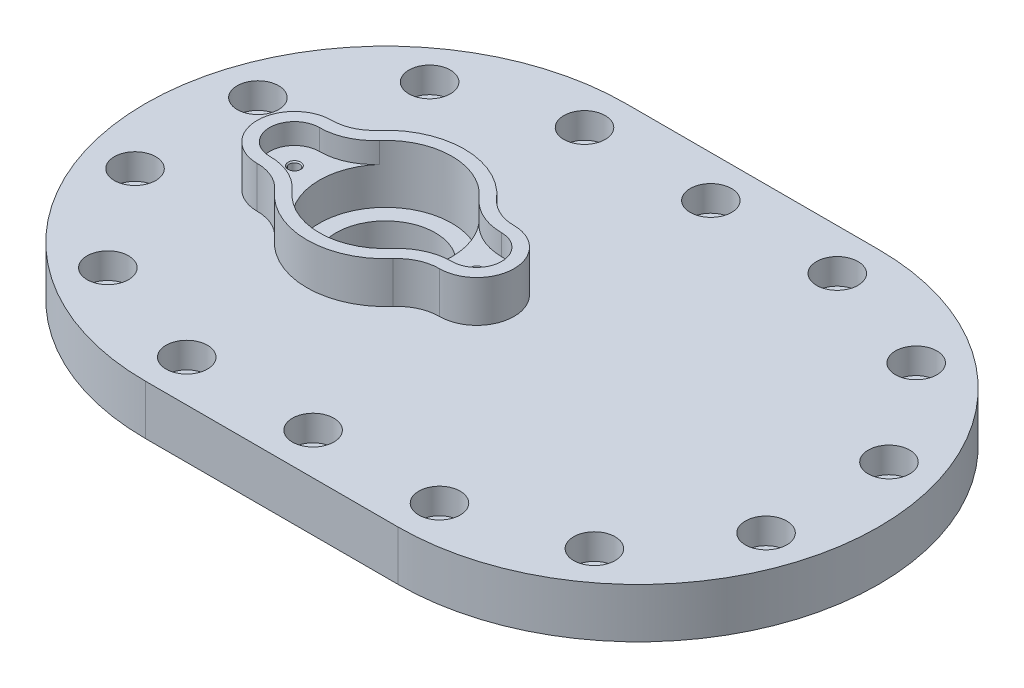
SolidWorks part; units mm, degrees
note: The reader was unsure of these and kept them because the rebuilt part matched: shared geometry of "Sketch2<6>", "Sketch2<7>", "Sketch2<8>", "Sketch2<10>", "Sketch2<12>".
ref_plane "Ön Düzlem" through (0, 0, 0) normal (0, 0, 1) x (1, 0, 0)
ref_plane "Üst Düzlem" through (0, 0, 0) normal (0, 1, 0) x (1, 0, 0)
ref_plane "Sağ Düzlem" through (0, 0, 0) normal (1, 0, 0) x (0, 0, -1)
sketch "Sketch2" plane through (0, 0, 0) normal (0, 1, 0) x (1, 0, 0)
  line L0 (-61, 0) -> (0, 0) construction
  line L1 (-61, 58) -> (0, 58)
  line L2 (-61, -58) -> (0, -58)
  line L3 (-61, 6.7769) -> (-61, -6.7769) construction
  arc A0 (-61, 58) -> (-61, -58) centre (-61, 0) ccw
  arc A1 (0, -58) -> (0, 58) centre (0, 0) ccw
  circle A2 centre (-61, 0) radius 12
  circle A3 centre (-61, 0) radius 16
  arc A4 (-39, -6) -> (-39, 6) centre (-39, 0) ccw
  arc A6 (-48.9452, 10.5205) -> (-39, 6) centre (-39, 19.2) ccw
  arc A7 (-48.9452, -10.5205) -> (-39, -6) centre (-39, -19.2) cw
  arc A8 (-73.0548, -10.5205) -> (-83, -6) centre (-83, -19.2) ccw
  arc A9 (-83, -6) -> (-83, 6) centre (-83, 0) cw
  arc A10 (-73.0548, 10.5205) -> (-83, 6) centre (-83, 19.2) cw
  arc A11 (-46.6849, -12.4932) -> (-39, -9) centre (-39, -19.2) cw
  arc A12 (-39, -9) -> (-39, 9) centre (-39, 0) ccw
  arc A13 (-46.6849, 12.4932) -> (-39, 9) centre (-39, 19.2) ccw
  arc A14 (-75.3151, 12.4932) -> (-83, 9) centre (-83, 19.2) cw
  arc A15 (-83, -9) -> (-83, 9) centre (-83, 0) cw
  arc A16 (-75.3151, -12.4932) -> (-83, -9) centre (-83, -19.2) ccw
  arc A18 (-75.3151, 12.4932) -> (-46.6849, 12.4932) centre (-61, 0) cw
  arc A19 (-75.3151, -12.4932) -> (-46.6849, -12.4932) centre (-61, 0) ccw
  circle A20 centre (-39, 0) radius 1.25
  circle A21 centre (-83, 0) radius 1.25
  circle A22 centre (0, 48) radius 2.75
  circle A23 centre (28.2137, 38.8328) radius 2.75
  circle A24 centre (45.6507, 14.8328) radius 2.75
  circle A25 centre (45.6507, -14.8328) radius 2.75
  circle A26 centre (28.2137, -38.8328) radius 2.75
  circle A27 centre (0, -48) radius 2.75
  circle A32 centre (-28.2137, 38.8328) radius 2.75 [skipped]
  circle A33 centre (-45.6507, 14.8328) radius 2.75 [skipped]
  circle A34 centre (-45.6507, -14.8328) radius 2.75 [skipped]
  circle A35 centre (-28.2137, -38.8328) radius 2.75 [skipped]
  circle A36 centre (-61, 48) radius 2.75
  circle A41 centre (-61, -48) radius 2.75
  circle A42 centre (-89.2137, -38.8328) radius 2.75
  circle A43 centre (-106.6507, -14.8328) radius 2.75
  circle A44 centre (-106.6507, 14.8328) radius 2.75
  circle A45 centre (-89.2137, 38.8328) radius 2.75
  circle A46 centre (-32.7863, 38.8328) radius 2.75 [skipped]
  circle A47 centre (-15.3493, 14.8328) radius 2.75 [skipped]
  circle A48 centre (-15.3493, -14.8328) radius 2.75 [skipped]
  circle A49 centre (-32.7863, -38.8328) radius 2.75 [skipped]
  circle A50 centre (-30.5, -48) radius 2.75
  circle A51 centre (-30.5, 48) radius 2.75
  circle A52 centre (28.2137, 38.8328) radius 5
  circle A53 centre (45.6507, 14.8328) radius 5
  circle A54 centre (45.6507, -14.8328) radius 5
  circle A55 centre (28.2137, -38.8328) radius 5
  circle A56 centre (0, -48) radius 5
  circle A57 centre (-30.5, -48) radius 5
  circle A58 centre (-61, -48) radius 5
  circle A59 centre (-89.2137, -38.8328) radius 5
  circle A60 centre (-106.6507, -14.8328) radius 5
  circle A61 centre (-106.6507, 14.8328) radius 5
  circle A62 centre (-89.2137, 38.8328) radius 5
  circle A63 centre (-61, 48) radius 5
  circle A64 centre (-30.5, 48) radius 5
  circle A65 centre (0, 48) radius 5
  point P3 (-30.5, 0)
  point P21 (-61, 0)
  point P69 (0, 0)
  point P90 (-61, 0)
  dimension "D3" = 24
  dimension "D4" = 32
  dimension "D6" = 6
  dimension "D8" = 19
  dimension "D9" = 19
  dimension "D10" = 2.5
  dimension "D11" = 5.5
  dimension "D15" = 5.5
  dimension "D20" = 5.5
  dimension "D21" = 48
  dimension "D22" = 10
  dimension "D1" = 116
  dimension "D2" = 61
  dimension "D5" = 44
  dimension "D12" = 48
  dimension "D14" = 48
  dimension "D16" = 48
  dimension "D18" = 48
  dimension "D19" = 48
  dimension "D7" = 3
  dimension "D13" = 10
  dimension "D17" = 10
extrude "Boss-Extrude4" add sketch "Sketch2" along normal blind 12 contours L2 A1 L1 A0 A65 A64 A63 A62 A61 A60 A59 A58 A57 A56 A55 A54 A53 A52 A19 A16 A15 A14 A18 A13 A12 A11
extrude "Boss-Extrude5" add sketch "Sketch2<6>" along normal blind 8 separate body contours A3 A2
sketch "Sketch2<6>" plane through (0, 0, 0) normal (0, 1, 0) x (1, 0, 0) same geometry as "Sketch2"
extrude "Boss-Extrude6" add sketch "Sketch2<7>" along normal blind 17 contours A3 A7 A4 A6 A20 | A3 A10 A9 A8 A21
sketch "Sketch2<7>" plane through (0, 0, 0) normal (0, 1, 0) x (1, 0, 0) same geometry as "Sketch2"
extrude "Boss-Extrude7" add sketch "Sketch2<8>" along normal blind 22 contours A16 A19 A11 A12 A13 A18 A14 A15 A10 A3 A6 A4 A7 A8 A9
sketch "Sketch2<8>" plane through (0, 0, 0) normal (0, 1, 0) x (1, 0, 0) same geometry as "Sketch2"
extrude "Boss-Extrude9" add sketch "Sketch2<10>" along normal blind 17 contours A21 | A20
sketch "Sketch2<10>" plane through (0, 0, 0) normal (0, 1, 0) x (1, 0, 0) same geometry as "Sketch2"
hole_wizard "M3 Tapped Hole2" positions "Sketch6" profile "Sketch7" tap size "M3" standard "ISO"
sketch "Sketch6" plane through (0, 17, 0) normal (0, 1, 0) x (1, 0, 0)
  point P0 (-39, 0)
  point P3 (-83, 0)
cosmetic thread "Hole Thread3" parameters "D1"=15, "D2"=3
cosmetic thread "Hole Thread4" parameters "D1"=15, "D2"=3
sketch "Sketch7" plane through (-39, 17, 0) normal (1, 0, 0) x (0, 0, 1)
  line L0 (0, 0) -> (0, 10.7511)
  line L1 (0, 10.7511) -> (1.25, 10)
  line L2 (1.25, 10) -> (1.25, 0.275)
  line L3 (1.25, 0.275) -> (1.525, 0)
  line L5 (1.525, 0) -> (0, 0)
  line L6 (-1.25, 0.275) -> (-1.525, 0) construction
  line L10 (0, 10.7511) -> (-1.25, 10) construction
  line L11 (0, -6.35) -> (0, 107.95) construction
  dimension "Tap Drill Dia." = 2.5
  dimension "Tap Drill Depth" = 10
  dimension "Near C'Sink Dia." = 3.05
  dimension "Near C'Sink Angle" = 90
  dimension "Drill Angle" = 118
sketch "Sketch11" plane through (0, 0, 0) normal (0, -1, 0) x (1, 0, 0)
  circle A0 centre (0, 0) radius 12
  dimension "D1" = 24
extrude "Cut-Extrude1" cut sketch "Sketch11" against normal blind 1
sketch "Sketch12" plane through (0, 0, 0) normal (0, -1, 0) x (1, 0, 0)
  circle A0 centre (0, 0) radius 8
  dimension "D1" = 16
extrude "Cut-Extrude2" cut sketch "Sketch12" against normal blind 6
chamfer "Chamfer1" distance 1 angle 45 1 edges at (0, 0, -12)
extrude "Boss-Extrude10" add sketch "Sketch2<12>" along normal blind 5.8 contours A56 A27 | A55 A26 | A54 A25 | A53 A24 | A52 A23 | A65 A22 | A64 A51 | A63 A36 | A62 A45 | A61 A44 | A60 A43 | A59 A42 | A58 A41 | A57 A50
sketch "Sketch2<12>" plane through (0, 0, 0) normal (0, 1, 0) x (1, 0, 0) same geometry as "Sketch2"
